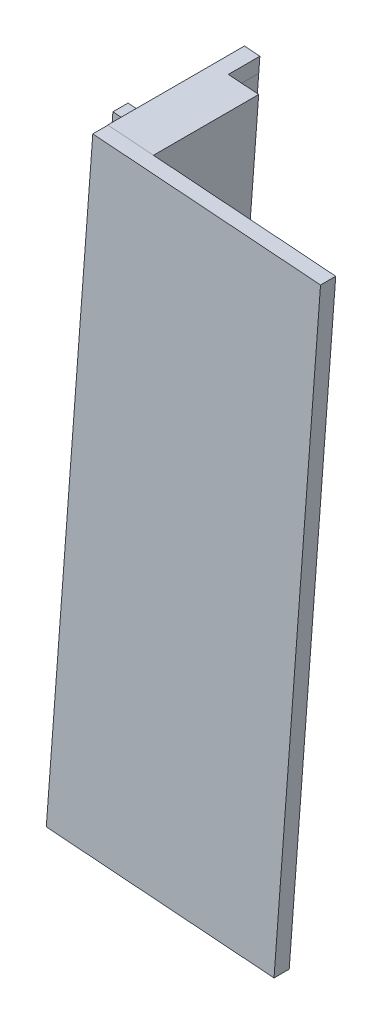
SolidWorks part; units mm, degrees
material "ABS"
ref_plane "Front Plane" through (0, 0, 0) normal (0, 0, 1) x (1, 0, 0)
ref_plane "Top Plane" through (0, 0, 0) normal (0, 1, 0) x (1, 0, 0)
ref_plane "Right Plane" through (0, 0, 0) normal (1, 0, 0) x (0, 0, -1)
sketch "Sketch2" plane through (0, 0, 0) normal (0, 0, 1) x (1, 0, 0)
  line L14 (-9.7013, -34.4358) -> (-2.6091, -34.965)
  line L15 (-9.7013, -34.4358) -> (-9.0965, -26.3303)
  line L16 (-8.2649, -15.1853) -> (-7.6601, -7.0798)
  line L17 (-2.0042, -26.8595) -> (-9.0965, -26.3303)
  line L18 (-2.0042, -26.8595) -> (-1.1726, -15.7145)
  line L19 (-8.2649, -15.1853) -> (-1.1726, -15.7145)
  line L20 (-0.5678, -7.609) -> (-7.6601, -7.0798)
  line L21 (-0.5678, -7.609) -> (0, 0)
  line L22 (0.9376, -1.0888) -> (-1.973, -40.0963)
  line L23 (-3.0619, -41.0339) -> (-2.6091, -34.965)
  line L24 (11.1321, -42.093) -> (-3.0619, -41.0339)
  line L25 (-1.973, -40.0963) -> (13.2342, -41.231)
  line L26 (14.1088, -2.0716) -> (0.9376, -1.0888)
  line L27 (0, 0) -> (14.1844, -1.0584)
  line L28 (-1.973, -40.0963) -> (-2.0486, -41.1095)
  line L29 (0.9376, -1.0888) -> (1.0132, -0.0756)
  dimension "D1" = 1.016
  dimension "D2" = 8.128
  dimension "D3" = 7.0923
  dimension "D4" = 11.145
  dimension "D5" = 14.2238
  dimension "D6" = 13.2078
  dimension "D7" = 13.1712
  dimension "D8" = 39.0076
  dimension "D9" = 15.2073
  dimension "D10" = 14.1941
  dimension "D11" = 7.1119
  dimension "D12" = 8.1055
  dimension "D13" = 1.016
  dimension "D14" = 1.016
  dimension "D15" = 90
  dimension "D16" = 90
  dimension "D17" = 1.016
  dimension "D18" = 7.6302
extrude "Boss-Extrude2" add sketch "Sketch2" along normal blind 9 contours L22 L29 L27 L21 L20 L16 L19 L18 L17 L15 L14 L23 L24 L28 region at (-8.9753, -30.4146, 0)
sketch "Sketch3" plane through (-2.609, -34.965, 0) normal (-0.0744, -0.9972, 0) x (0.9972, -0.0744, 0)
  line L0 (-7.1121, 9) -> (-0.0001, 9) construction
  line L1 (-7.1121, 9) -> (-7.1121, 0) construction
  line L2 (-0.0001, 9) -> (-0.0001, 0) construction
  line L3 (0, 0) -> (-7.1121, 0) construction
  line L4 (-7.1121, 9) -> (-0.0001, 9)
  line L5 (-7.1121, 1) -> (-7.1121, 0)
  line L6 (-0.0001, 9) -> (-0.0001, 0)
  line L7 (0, 0) -> (-7.1121, 0)
  line L8 (-7.1121, 9) -> (-54.2204, 9)
  line L9 (-7.1121, 0) -> (-0.0001, 0)
  line L10 (-7.1121, 0) -> (-7.1121, 1)
  line L11 (-7.1121, 1) -> (-0.0001, 1)
  line L12 (-0.0001, 0) -> (-0.0001, 1)
  line L13 (-54.2204, 9) -> (-54.2204, 1)
  line L14 (-54.2204, 1) -> (-7.1121, 1)
  line M6 (-7.1121, 9) -> (-7.1121, 0)
  dimension "D1" = 54.2203
  dimension "1mm" = 1
extrude "Cut-Extrude3" cut sketch "Sketch3" against normal blind 29.526 and the other way through all contours L11 L6 L4 M6 | L13 L14 L8 M6 region at (-33.1902, -32.6831, 5) region at (-6.1552, -34.7004, 5)
sketch "Sketch4" plane through (1.0132, -0.0756, 0) normal (0.9972, -0.0744, 0) x (0, 0, -1)
  line L0 (-9, -41.148) -> (-9, 0)
  line L1 (-9, -41.148) -> (-10, -41.148)
  line L2 (-9, 0) -> (-10, 0)
  line L3 (-10, -41.148) -> (-10, 0)
  dimension "D1" = 1
extrude "Boss-Extrude3" add sketch "Sketch4" along normal blind 14.032 and the other way blind 1
sketch "Sketch5" plane through (1.0132, -0.0756, 0) normal (0.9972, -0.0744, 0) x (0, 0, -1)
  line L0 (0, -1.016) -> (0, -40.132) construction
  line L1 (0, -40.132) -> (0, -41.148) construction
  line L2 (0, -1.016) -> (0, 0) construction
  line L3 (-9, -41.148) -> (0, -41.148) construction
  line L4 (-9, 0) -> (0, 0) construction
  line L5 (-9, -1.016) -> (-9, -40.132) construction
  line L6 (-9, -1.016) -> (-9, 0) construction
  line L7 (-9, -40.132) -> (-9, -41.148) construction
  line L8 (0, -1.016) -> (0, -40.132)
  line L9 (0, -40.132) -> (0, -41.148)
  line L10 (0, -1.016) -> (0, 0)
  line L11 (-9, -41.148) -> (0, -41.148)
  line L12 (-9, 0) -> (0, 0)
  line L13 (-9, -1.016) -> (-9, -40.132)
  line L14 (-9, -1.016) -> (-9, 0)
  line L15 (-9, -40.132) -> (-9, -41.148)
  line L16 (-4.5, -40.132) -> (-4.5, -1.016)
  line L17 (-9, -40.132) -> (0, -40.132) construction
  line L18 (-9, -1.016) -> (0, -1.016) construction
  line L19 (-4.5, -40.132) -> (-4.5, -41.148)
  line L20 (-4.5, -1.016) -> (-4.5, 0)
  line L21 (-2.0724, 0) -> (-2.0724, -41.148)
  line M2 (0, -1.016) -> (-9, -1.016)
  line M3 (-9, -1.016) -> (-9, -40.132)
  line M4 (-9, -40.132) -> (0, -40.132)
  dimension "D1" = 2.0724
extrude "Boss-Extrude4" add sketch "Sketch5" along normal blind 2 contours L16 M4 M2 M3 | L19 L15 L11 M4 | L20 L12 L14 M2 | L21 L16 M2 M4 | L21 L12 L20 M2 | L21 L19 L11 M4 region at (0.9754, -0.5822, 3.2862) region at (-0.5177, -20.5926, 3.2862) region at (-2.0108, -40.6029, 3.2862) region at (0.9754, -0.5822, 6.75) region at (-0.5177, -20.5926, 6.75) region at (-2.0108, -40.6029, 6.75)
hole_wizard "CSK for #3 Flat Head Socket Cap Screw1" positions "Sketch7" profile "Sketch6" countersink size "#3" standard "ANSI Inch" end condition through all
sketch "Sketch7" plane through (0, 0, 1) normal (0, 0, 1) x (1, 0, 0)
  line L0 (-2.0042, -26.8595) -> (-9.0965, -26.3303) construction
  line L1 (-0.5678, -7.609) -> (-7.6601, -7.0798) construction
  line L2 (-8.2649, -15.1853) -> (-7.6601, -7.0798) construction
  line L3 (-9.7013, -34.4358) -> (-9.0965, -26.3303) construction
  point P0 (-4.4126, -11.3465)
  point P2 (-5.848, -30.5838)
  dimension "D1" = 4
  dimension "D2" = 4.0132
  dimension "D3" = 3.556
  dimension "D4" = 3.556
sketch "Sketch6" plane through (-4.4126, -11.3465, 1) normal (1, 0, 0) x (0, -1, 0)
  line L0 (0, 0) -> (0, 1)
  line L1 (0, 1) -> (1.397, 1)
  line L2 (1.397, 1) -> (1.397, 1.6947)
  line L3 (1.397, 1.6947) -> (2.8702, 0)
  line L5 (2.8702, 0) -> (0, 0)
  line L6 (-1.397, 1.6947) -> (-2.8702, 0) construction
  line L11 (0, -6.35) -> (0, 107.95) construction
  dimension "Thru Hole Dia." = 2.794
  dimension "Thru Hole Depth" = 1
  dimension "Near C'Sink Dia." = 5.7404
  dimension "Near C'Sink Angle" = 82
